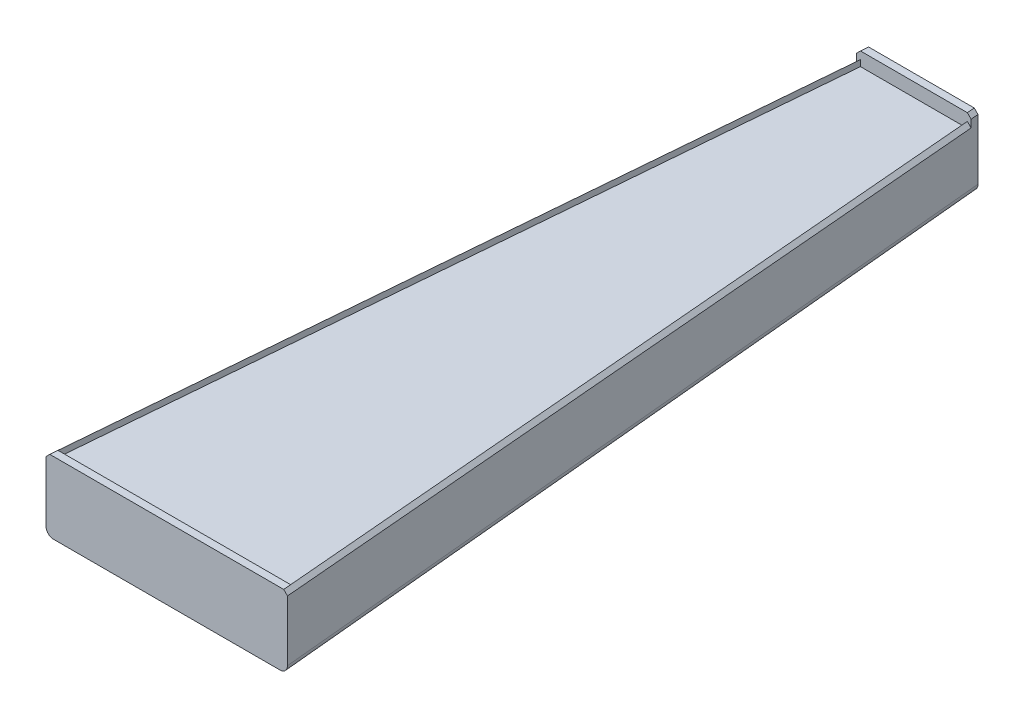
SolidWorks part; units mm, degrees
ref_plane "Front Plane" through (0, 0, 0) normal (0, 0, 1) x (1, 0, 0)
ref_plane "Top Plane" through (0, 0, 0) normal (0, 1, 0) x (1, 0, 0)
ref_plane "Right Plane" through (0, 0, 0) normal (1, 0, 0) x (0, 0, -1)
sketch "Sketch1" plane through (0, 0, 0) normal (0, 1, 0) x (1, 0, 0)
  line L0 (15, 0) -> (-15, 0)
  line L1 (0, 0) -> (0, -200) construction
  line L2 (32, -200) -> (-32, -200)
  line L3 (-32, -200) -> (-15, 0)
  line L4 (32, -200) -> (15, 0)
  dimension "\"neck length" = 200
extrude "Boss-Extrude1" add sketch "Sketch1" along normal blind 19
sketch "Sketch4" plane through (0, 0, 0) normal (1, 0, 0) x (0, 0, -1)
  line L0 (-200, 0) -> (0, 0)
  line L1 (0, 0) -> (0, 2)
  line L2 (0, 19) -> (0, 0) construction
  line L4 (0, 2) -> (-200, 0)
extrude "Cut-Extrude1" cut sketch "Sketch4" against normal through all both and the other way through all
shell "Shell1" thickness 4 removed face at (0, 1, 100)
fillet "Fillet2" 2 edges at (23.5, 1, 100) (19.4856, 1, 100) type full round first side face at (23.5, 10, 100) second side face at (19.4856, 6, 100) middle face at (0, 1, 100)
fillet "Fillet3" 2 edges at (-23.5, 1, 100) (-19.4856, 1, 100) type full round first side face at (-23.5, 10, 100) second side face at (-19.4856, 6, 100) middle face at (0.0008, 1, 100)
sketch "Sketch5" plane through (0, 19, 0) normal (0, 1, 0) x (1, 0, 0)
  line L0 (-15, 0) -> (-15.1693, -1.9912)
  line L1 (-15, 0) -> (-32, -200) construction
  line L2 (-15.1693, -1.9912) -> (15.1693, -1.9912)
  line L3 (32, -200) -> (15, 0) construction
  line L4 (15.1693, -1.9912) -> (15, 0)
  line L5 (15, 0) -> (-15, 0)
extrude "Boss-Extrude2" add sketch "Sketch5" along normal blind 2
chamfer "Chamfer1" distance 1 angle 45 2 edges at (23.5846, 19, 100.9956) (-23.5846, 19, 100.9956)
chamfer "Chamfer2" distance 1 angle 45 2 edges at (15.0846, 21, 0.9956) (-15.0846, 21, 0.9956)
sketch "Sketch6" plane through (0, 19, 0) normal (0, 1, 0) x (1, 0, 0)
  line L0 (-14.1656, -1.9912) -> (14.1656, -1.9912)
  line L1 (0, -1.9912) -> (0, -197.9912) construction
  line L2 (-30.8256, -197.9912) -> (30.8256, -197.9912)
  line L3 (30.9964, -200) -> (14.1656, -1.9912) construction
  line L4 (30.8256, -197.9912) -> (14.1656, -1.9912)
  line L5 (-14.1656, -1.9912) -> (-30.8256, -197.9912)
  line L6 (-14.1656, -1.9912) -> (-30.9964, -200) construction
extrude "Cut-Extrude2" cut sketch "Sketch6" against normal blind 1.6
equation "\"neck length\"= 200mm"
